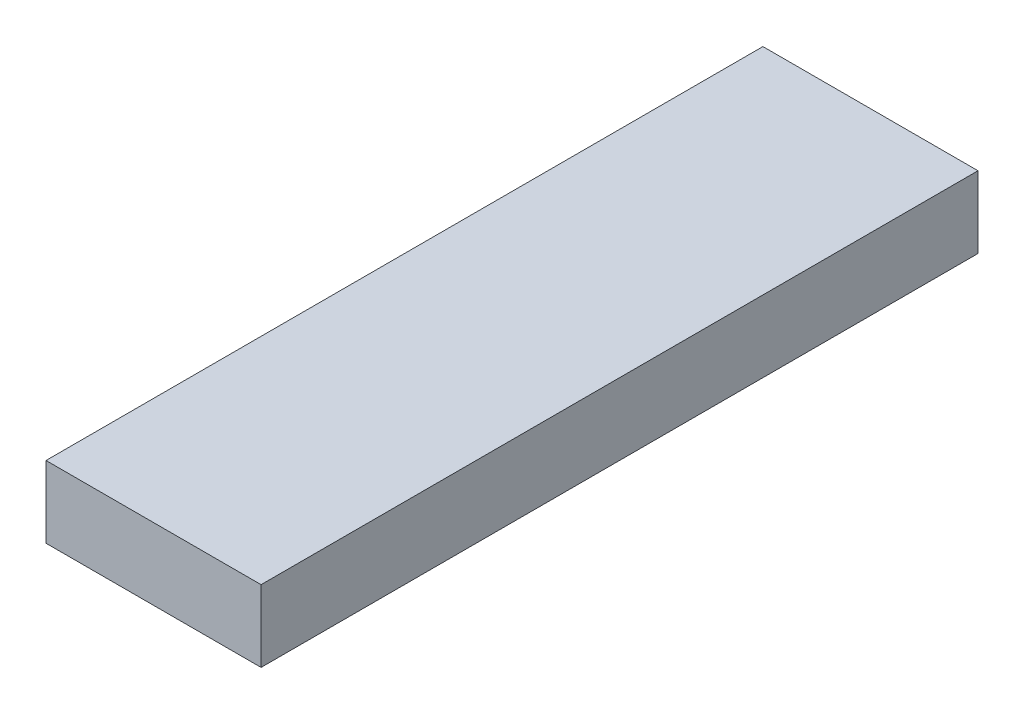
SolidWorks part; units mm, degrees
ref_plane "Front Plane" through (0, 0, 0) normal (0, 0, 1) x (1, 0, 0)
ref_plane "Top Plane" through (0, 0, 0) normal (0, 1, 0) x (1, 0, 0)
ref_plane "Right Plane" through (0, 0, 0) normal (1, 0, 0) x (0, 0, -1)
sketch "Sketch1" plane through (0, 0, 0) normal (0, 1, 0) x (1, 0, 0)
  line L1 (0, 0) -> (30, 0)
  line L2 (0, 0) -> (0, 100)
  line L3 (0, 100) -> (30, 100)
  line L4 (30, 0) -> (30, 100)
  dimension "D1" = 100
  dimension "D2" = 30
extrude "Boss-Extrude1" add sketch "Sketch1" along normal blind 10
ref_plane "Plane1" through (15, 0, 0) normal (-1, 0, 0) x (0, 0, 1)
